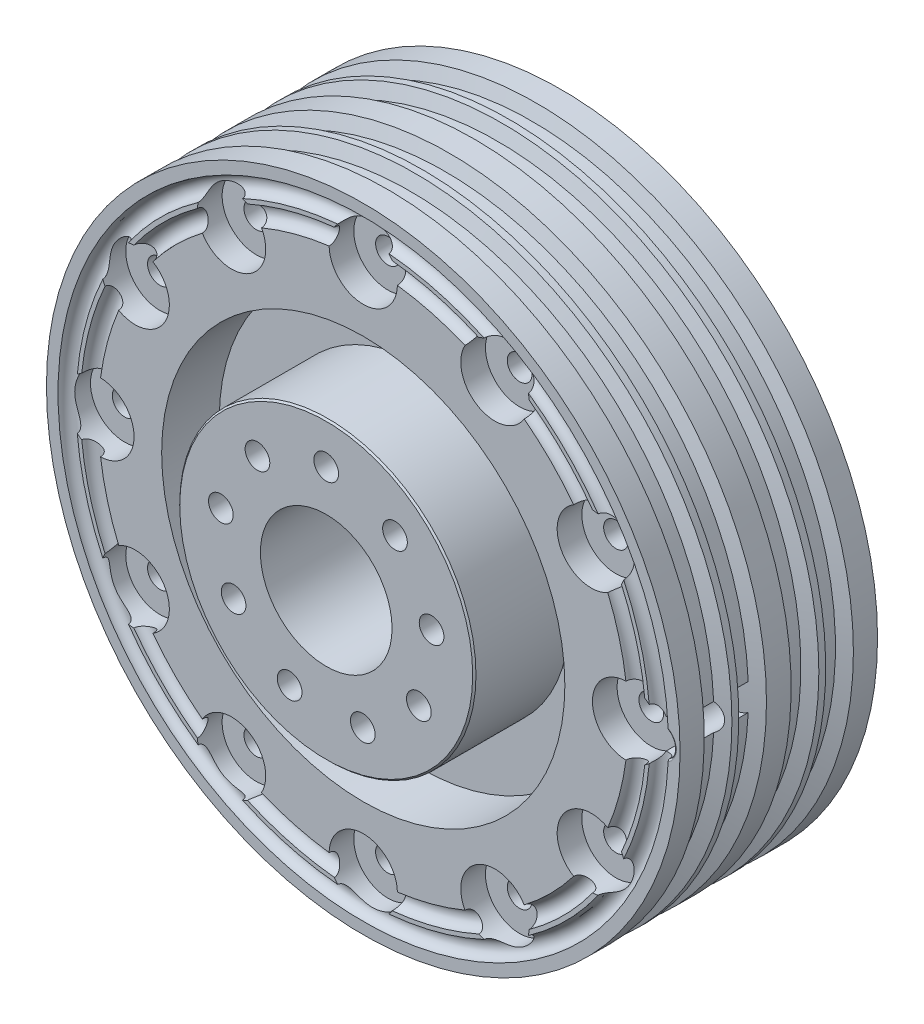
SolidWorks part; units mm, degrees
ref_plane "Front Plane" through (0, 0, 0) normal (0, 0, 1) x (1, 0, 0)
ref_plane "Top Plane" through (0, 0, 0) normal (0, 1, 0) x (1, 0, 0)
ref_plane "Right Plane" through (0, 0, 0) normal (1, 0, 0) x (0, 0, -1)
sketch "Sketch2" plane through (0, 0, 0) normal (1, 0, 0) x (0, 0, -1)
  line L0 (25.8266, -6.7872) -> (-20.1734, -6.7872) construction
  line L1 (-20.1734, -1.7872) -> (25.8266, -1.7872)
  line L2 (25.8266, -6.7872) -> (-20.1734, -6.7872)
  line L5 (25.8266, -1.7872) -> (25.8266, -6.7872) construction
  line L6 (7.109, 30.1128) -> (7.109, 10.1339) construction
  line L7 (-20.1734, -1.7872) -> (-20.1734, -6.7872)
  line L8 (25.8266, -1.7872) -> (25.8266, -6.7872)
  line L9 (-20.1734, -4.2872) -> (25.8266, -4.2872) construction
  line L10 (2.8266, -4.2872) -> (2.8266, 31.7128) construction
  line L11 (2.8266, 31.7128) -> (-14.0396, 31.7128) construction
  line L12 (8.5266, 31.7128) -> (-2.8734, 31.7128)
  line L13 (-2.8734, 31.7128) -> (-3.4557, 30.1128)
  line L14 (-3.4557, 30.1128) -> (-5.6557, 30.1128)
  line L15 (-5.6557, 30.1128) -> (-6.2381, 31.7128)
  line L16 (-6.2381, 31.7128) -> (1.3266, 31.7128)
  line L17 (1.3266, 31.7128) -> (0.7443, 30.1128)
  line L18 (0.7443, 30.1128) -> (-1.4557, 30.1128)
  line L19 (-1.4557, 30.1128) -> (-2.0381, 31.7128)
  line L20 (-2.0381, 31.7128) -> (-9.1734, 31.7128)
  line L21 (0.7443, 30.1128) -> (0.7443, 32.537) construction
  line L22 (-1.4557, 30.1128) -> (-1.4557, 32.537) construction
  line L23 (-9.1734, 31.7128) -> (-9.1734, -1.7872)
  line L24 (-9.1734, -1.7872) -> (14.8266, -1.7872)
  line L25 (2.8266, -1.7872) -> (2.8266, 31.7128)
  line L26 (14.8266, 31.7128) -> (14.8266, -1.7872)
  line L27 (7.6913, 31.7128) -> (14.8266, 31.7128)
  line L28 (7.109, 30.1128) -> (7.6913, 31.7128)
  line L29 (4.909, 30.1128) -> (7.109, 30.1128)
  line L30 (4.3266, 31.7128) -> (4.909, 30.1128)
  line L31 (11.8913, 31.7128) -> (4.3266, 31.7128)
  line L32 (11.309, 30.1128) -> (11.8913, 31.7128)
  line L33 (9.109, 30.1128) -> (11.309, 30.1128)
  line L34 (8.5266, 31.7128) -> (9.109, 30.1128)
  line L35 (4.909, 30.1128) -> (4.909, 33.6348) construction
  line L36 (9.109, 30.1128) -> (9.109, 10.1339) construction
  dimension "D1" = 46
  dimension "D2" = 5
  dimension "D3" = 33.5
  dimension "D4" = 1.6
  dimension "D5" = 2.2
  dimension "D6" = 20
  dimension "D7" = 20
  dimension "D8" = 12
  dimension "D9" = 1.5
  dimension "D10" = 1.6
  dimension "D11" = 2
revolve "Revolve1" add sketch "Sketch2" angle 360 about L2 region at (0, 14.6003, 3.1896) region at (0, 14.6003, -8.8429)
ref_axis "Axis1" through (0, -6.7872, 26.1499) along (0, 0, -1)
sketch "Sketch3" plane through (0, 0, -14.8266) normal (0, 0, -1) x (-1, 0, 0)
  line L0 (38.5, -6.7872) -> (36, -6.7872) construction
  circle A0 centre (0, -6.7872) radius 38.5 construction
  circle A1 centre (36, -6.7872) radius 1.85
  dimension "D1" = 2.5
  dimension "D2" = 3.7
extrude "Cut-Extrude1" cut sketch "Sketch3" against normal up to surface (9.6074 mm away) up to face at (-36.9, -6.7872, -4.909)
ref_plane "Plane1" through (0, -6.7872, 0) normal (0, 1, 0) x (1, 0, 0)
fillet "Fillet1" radius 0.2 1 edges at (-36, -4.9372, -14.8266)
sketch "Sketch7" plane through (0, 0, 9.1734) normal (0, 0, 1) x (1, 0, 0)
  line L0 (38.5, -6.7872) -> (36, -6.7872) construction
  line L1 (32.6518, -6.7872) -> (-32.6518, -6.7872) construction
  circle A0 centre (0, -6.7872) radius 38.5 construction
  circle A1 centre (36, -6.7872) radius 1.85
  dimension "D1" = 3.7
  dimension "D2" = 2.5
extrude "Cut-Extrude2" cut sketch "Sketch7" against normal up to surface (10.2634 mm away) up to face at (-36.9, -6.7872, -0.7443)
fillet "Fillet2" radius 0.2 1 edges at (37.85, -6.7872, 9.1734)
ref_plane "Plane2" through (0, 0, -2.8266) normal (0, 0, 1) x (1, 0, 0)
sketch "Sketch15" plane through (0, 0, 9.1734) normal (0, 0, 1) x (1, 0, 0)
  circle A0 centre (0, -6.7872) radius 24.5
  circle A1 centre (0, -6.7872) radius 38.5 construction
  dimension "D1" = 14
extrude "Cut-Extrude3" cut sketch "Sketch15" against normal blind 7
sketch "Sketch16" plane through (0, 0, -14.8266) normal (0, 0, -1) x (-1, 0, 0)
  circle A1 centre (0, -6.7872) radius 24.5
  circle A2 centre (0, -6.7872) radius 24.5
  dimension "D1" = 0
extrude "Cut-Extrude4" cut sketch "Sketch16" against normal blind 5
sketch "Sketch17" plane through (0, -6.7872, 0) normal (0, 1, 0) x (1, 0, 0)
  line L0 (0, -9.1734) -> (35.9909, -9.1734) construction
  line L1 (-38.5, -9.1734) -> (38.5, -9.1734) construction
  line L2 (35.9909, -9.1734) -> (33.2909, -9.1734) construction
  circle A0 centre (35.9909, -9.1734) radius 1.1
  circle A1 centre (33.2909, -9.1734) radius 1.1
  dimension "D1" = 2.7
  dimension "D3" = 2.2
revolve "Cut-Revolve1" cut sketch "Sketch17" angle 360 about axis through (0, -6.7872, 26.1499) along (0, 0, -1)
ref_plane "Plane3" through (0, 0, -2.8266) normal (0, 0, 1) x (1, 0, 0)
sketch "Sketch18" plane through (0, 0, -2.8266) normal (0, 0, 1) x (1, 0, 0)
  line L0 (0, -31.2872) -> (0, -41.6781) construction
  circle A0 centre (0, -6.7872) radius 24.5 construction
  circle A1 centre (0, -6.7872) radius 24.5 construction
  arc A6 (34.8496, -5.0904) -> (34.8496, -8.484) centre (0, -6.7872) ccw construction
  circle A7 centre (0, -36.4826) radius 4.15
  circle A8 centre (0, -36.4826) radius 1.5
  dimension "D1" = 8.3
  dimension "D2" = 3
sketch "Sketch20" plane through (0, 0, 9.1734) normal (0, 0, 1) x (1, 0, 0)
  line L0 (0, -31.2872) -> (0, -38.7872) construction
  circle A0 centre (0, -38.7872) radius 1.5
  circle A1 centre (0, -38.7872) radius 4.15
  arc M5 (37.049, -8.5484) -> (37.049, -5.0259) centre (0, -6.7872) cw
  dimension "D1" = 3
  dimension "D2" = 8.3
  dimension "D3" = 7.5
extrude "Cut-Extrude5" cut sketch "Sketch20" against normal blind 3 contours A0 | A1 A0 M5 | A1 region at (0, -38.7872, 9.1734) region at (-4.0326, -38.7872, 9.1734)
extrude "Cut-Extrude6" cut sketch "Sketch20<3>" against normal blind 11.5 contours A0 region at (0, -38.7872, 9.1734)
sketch "Sketch20<3>" plane through (0, 0, 9.1734) normal (0, 0, 1) x (1, 0, 0) same geometry as "Sketch20"
sketch "Sketch21" plane through (0, 0, 2.1734) normal (0, 0, 1) x (1, 0, 0)
  circle A0 centre (0, -6.7872) radius 8
  circle A1 centre (0, -6.7872) radius 18
  circle A2 centre (0, -6.7872) radius 5
  dimension "D1" = 3
  dimension "D2" = 10
extrude "Boss-Extrude1" add sketch "Sketch21" along normal blind 11.5 contours A1 A0 region at (-17.4909, -6.7872, 2.1734)
pattern_circular "CirPattern1" count 12 every 30 about axis through (0, -6.7872, 26.1499) along (0, 0, -1) of "Cut-Extrude5", "Cut-Extrude6"
sketch "Sketch22" plane through (0, 0, 13.6734) normal (0, 0, 1) x (1, 0, 0)
  line L0 (0, 1.2128) -> (0, 11.2128) construction
  line L1 (0, -6.7872) -> (0, 6.2128) construction
  circle A0 centre (0, -6.7872) radius 8 construction
  circle A1 centre (0, -6.7872) radius 8 construction
  circle A2 centre (0, -6.7872) radius 18 construction
  circle A3 centre (0, -6.7872) radius 18 construction
  circle A4 centre (0, 6.2128) radius 1.5
  dimension "D1" = 3
  dimension "D2" = 13
extrude "Cut-Extrude7" cut sketch "Sketch22" against normal blind 5
pattern_circular "CirPattern2" count 9 every 40 about axis through (0, -6.7872, 26.1499) along (0, 0, -1) of "Cut-Extrude7"
mirror "Mirror1" about plane through (0, 0, -2.8266) normal (0, 0, 1) of "Boss-Extrude1", "CirPattern1", "Cut-Revolve1"
sketch "Sketch23" plane through (0, 0, -19.3266) normal (0, 0, -1) x (-1, 0, 0)
  circle A0 centre (0, -6.7872) radius 13.6
  circle A1 centre (0, -6.7872) radius 18
  circle M3 centre (0, -6.7872) radius 8
  dimension "D1" = 27.2
extrude "Cut-Extrude8" cut sketch "Sketch23" against normal up to surface (9.5 mm away) contours A0 M3 region at (13.2153, -6.7872, -19.3266) up to face at (0, -1.7872, -9.8266)
sketch "Sketch24" plane through (0, 0, -19.3266) normal (0, 0, -1) x (-1, 0, 0)
  circle A0 centre (0, -6.7872) radius 13.6
  circle A1 centre (0, -6.7872) radius 18
  circle A2 centre (0, -6.7872) radius 18
  dimension "D1" = 0
extrude "Cut-Extrude9" cut sketch "Sketch24" against normal blind 3
chamfer "Chamfer1" distance 0.5 angle 45 1 edges at (-13.6, -6.7872, -16.3266)
chamfer "Chamfer2" distance 0.2 angle 45 1 edges at (18, -6.7872, 13.6734)
